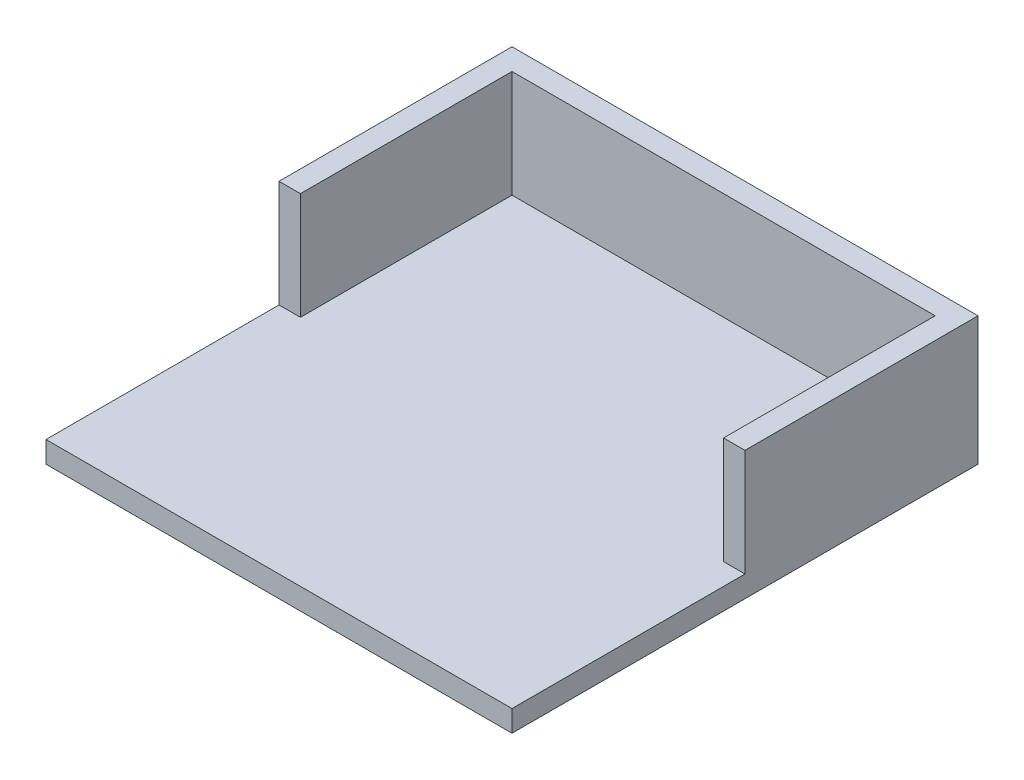
SolidWorks part; units mm, degrees
ref_plane "Front Plane" through (0, 0, 0) normal (0, 0, 1) x (1, 0, 0)
ref_plane "Top Plane" through (0, 0, 0) normal (0, 1, 0) x (1, 0, 0)
ref_plane "Right Plane" through (0, 0, 0) normal (1, 0, 0) x (0, 0, -1)
sketch "Sketch1" plane through (0, 0, 0) normal (0, 1, 0) x (1, 0, 0)
  line L1 (0, 0) -> (43.5, 0)
  line L2 (0, 0) -> (0, 43.5)
  line L3 (0, 43.5) -> (43.5, 43.5)
  line L4 (43.5, 0) -> (43.5, 43.5)
  dimension "D1" = 43.5
  dimension "D2" = 43.5
extrude "Boss-Extrude1" add sketch "Sketch1" along normal blind 2
sketch "Sketch2" plane through (0, 2, 0) normal (0, 1, 0) x (1, 0, 0)
  line L5 (0, 43.5) -> (43.5, 43.5)
  line L6 (0, 43.5) -> (0, 0)
  line L7 (0, 0) -> (43.5, 0)
  line L8 (2, 41.5) -> (2, 2)
  line L9 (2, 2) -> (41.5, 2)
  line L10 (41.5, 2) -> (41.5, 41.5)
  line L11 (41.5, 41.5) -> (2, 41.5)
  line L12 (2, 41.5) -> (2, 2)
  line L13 (2, 2) -> (41.5, 2)
  line L14 (41.5, 2) -> (41.5, 41.5)
  line L15 (41.5, 41.5) -> (2, 41.5)
  line L16 (43.5, 43.5) -> (43.5, 0)
  dimension "D1" = 2
extrude "Boss-Extrude2" add sketch "Sketch2" along normal blind 10
sketch "Sketch3" plane through (0, 12, 0) normal (0, 1, 0) x (1, 0, 0)
  line L0 (43.5, 0) -> (43.5, 43.5) construction
  line L1 (0, 0) -> (43.5, 0)
  line L2 (0, 0) -> (0, 21.75)
  line L3 (0, 21.75) -> (43.5, 21.75)
  line L4 (43.5, 0) -> (43.5, 21.75)
extrude "Cut-Extrude1" cut sketch "Sketch3" against normal blind 10
